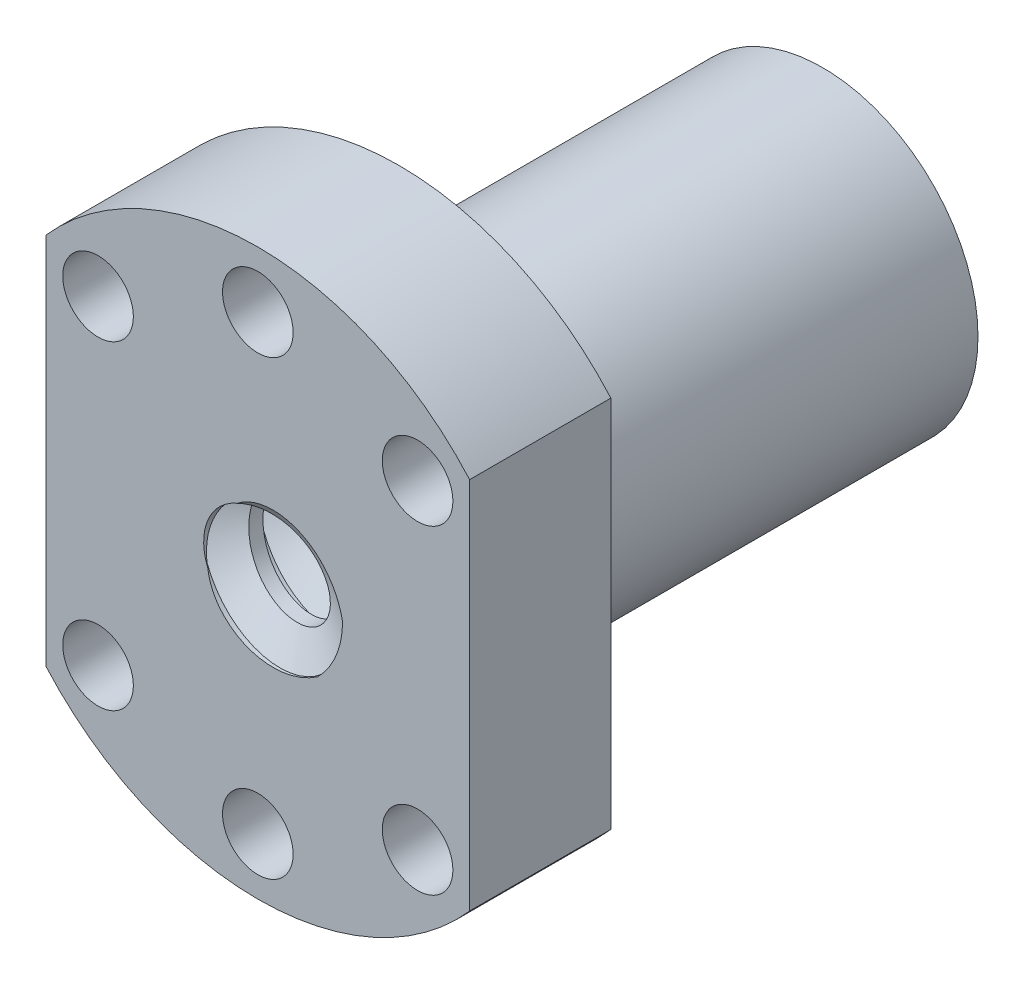
SolidWorks part; units mm, degrees
ref_plane "Front Plane" through (0, 0, 0) normal (0, 0, 1) x (1, 0, 0)
ref_plane "Top Plane" through (0, 0, 0) normal (0, 1, 0) x (1, 0, 0)
ref_plane "Right Plane" through (0, 0, 0) normal (1, 0, 0) x (0, 0, -1)
sketch "Sketch1" plane through (0, 0, 0) normal (0, 0, 1) x (1, 0, 0)
  line L0 (-15, 13.2288) -> (-15, -13.2288)
  line L1 (0, 20) -> (0, -20) construction
  line L2 (15, 13.2288) -> (15, -13.2288)
  line L3 (-11.3137, 11.3137) -> (0, 0) construction
  arc A0 (-15, -13.2288) -> (15, -13.2288) centre (0, 0) ccw
  circle A1 centre (-11.3137, 11.3137) radius 2.5
  circle A2 centre (0, 16) radius 2.5
  circle A3 centre (11.3137, 11.3137) radius 2.5
  circle A4 centre (16, 0) radius 2.5 [skipped]
  circle A5 centre (11.3137, -11.3137) radius 2.5
  circle A6 centre (0, -16) radius 2.5
  circle A7 centre (-11.3137, -11.3137) radius 2.5
  circle A8 centre (-16, 0) radius 2.5 [skipped]
  arc A9 (15, 13.2288) -> (-15, 13.2288) centre (0, 0) ccw
  circle A10 centre (0, 0) radius 6
  point P28 (0, 0)
  dimension "D1" = 40
  dimension "D3" = 5
  dimension "D5" = 45
  dimension "D7" = 12
  dimension "D2" = 15
  dimension "D4" = 16
  dimension "D6" = 8
extrude "Boss-Extrude1" add sketch "Sketch1" along normal blind 10
sketch "Sketch2" plane through (0, 0, 0) normal (0, 0, -1) x (-1, 0, 0)
  circle A1 centre (0, 0) radius 11
  circle A2 centre (0, 0) radius 6
  dimension "D1" = 22
  dimension "D2" = 12
extrude "Boss-Extrude2" add sketch "Sketch2" along normal blind 30
thread "Thread1" pitch 4 method extrude trim with start face yes trim with end face yes profile "Thread Profile1" start angle 0, offset 6, length 0, pitch 4, diameter 12
ref_plane "Plane1" through (-6, 0, 16) normal (0, -1, 0) x (-1, 0, 0)
sketch "Thread Profile1" plane through (-6, 0, 16) normal (0, -1, 0) x (-1, 0, 0)
  line L0 (0, 0) -> (0, 4) construction
  line L11 (0, 0) -> (0, 3.5)
  line L12 (0, 3.5) -> (-2.1651, 2.25)
  line L13 (-2.1651, 2.25) -> (-2.1651, 1.25)
  line L15 (-2.1651, 1.25) -> (0, 0)
  line L17 (-2.1651, 1.75) -> (0, 1.75) construction
  point P2 (0, 0)
  dimension "Pitch" = 4
  dimension "Profile_Angle" = 60
  dimension "Profile_Land" = 1
  dimension "Profile_Height" = 2.1651
